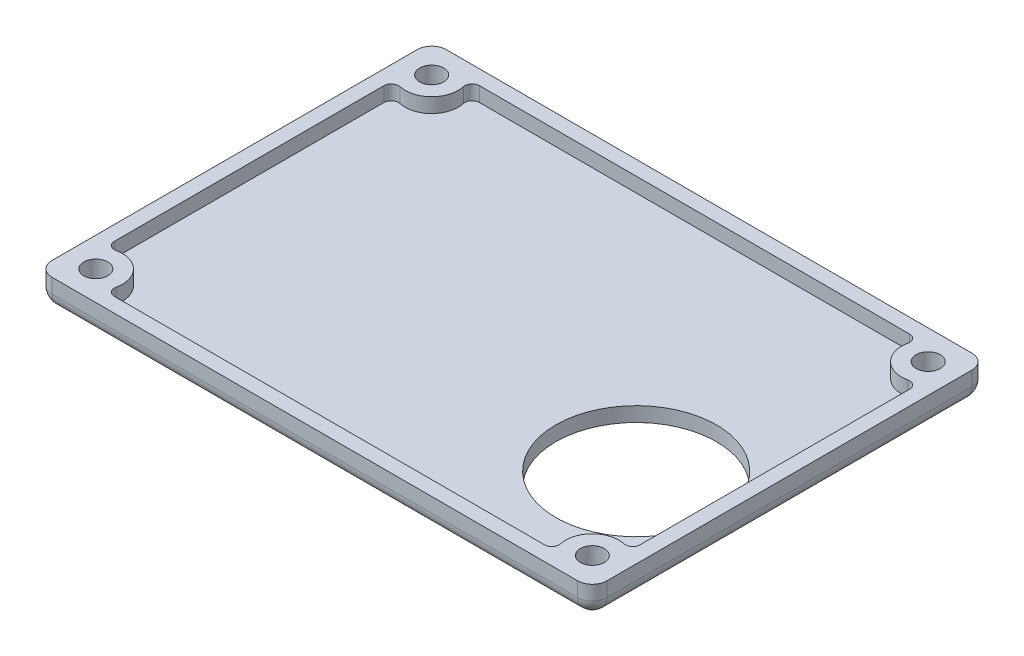
SolidWorks part; units mm, degrees
note: The reader was unsure of these and kept them because the rebuilt part matched: shared geometry of "Schizzo3<11>".
ref_plane "Piano frontale" through (0, 0, 0) normal (0, 0, 1) x (1, 0, 0)
ref_plane "Piano superiore" through (0, 0, 0) normal (0, 1, 0) x (1, 0, 0)
ref_plane "Piano destro" through (0, 0, 0) normal (1, 0, 0) x (0, 0, -1)
sketch "Schizzo1" plane through (0, 0, 0) normal (0, 1, 0) x (1, 0, 0)
  line L1 (-38, 27) -> (38, 27)
  line L2 (-38, 27) -> (-38, -27)
  line L3 (-38, -27) -> (38, -27)
  line L4 (38, 27) -> (38, -27)
  line L5 (-38, 27) -> (38, -27) construction
  line L6 (-38, -27) -> (38, 27) construction
  point P0 (0, 0)
  dimension "D1" = 76
  dimension "D2" = 54
extrude "Estrusione-Estrusione1" add sketch "Schizzo1" along normal blind 4
sketch "Schizzo2" plane through (0, 4, 0) normal (0, 1, 0) x (1, 0, 0)
  line L0 (38, 27) -> (-38, 27) construction
  line L1 (-36, 25) -> (36, 25)
  line L2 (-36, 25) -> (-36, -25)
  line L3 (-36, -25) -> (36, -25)
  line L4 (36, 25) -> (36, -25)
  line L5 (-36, 25) -> (36, -25) construction
  line L6 (-36, -25) -> (36, 25) construction
  line L7 (38, -27) -> (38, 27) construction
  point P0 (0, 0)
  dimension "D1" = 2
  dimension "D2" = 2
extrude "Taglio-Estrusione1" cut sketch "Schizzo2" against normal offset from surface (2 mm away) 2 up to face at (0, 0, 0)
sketch "Schizzo3" plane through (0, 2, 0) normal (0, 1, 0) x (1, 0, 0)
  line L2 (0, 42.9417) -> (0, -43.5578) construction
  line L3 (46.4844, 0) -> (-110.297, 0) construction
  line L10 (38, -27) -> (38, 27) construction
  line L13 (38, 27) -> (-38, 27) construction
  circle A8 centre (34, 23) radius 1.65
  circle A9 centre (34, 23) radius 3.65
  circle A10 centre (-34, 23) radius 3.65
  circle A13 centre (-34, 23) radius 1.65
  circle A18 centre (34, -23) radius 1.65
  circle A19 centre (34, -23) radius 3.65
  circle A20 centre (-34, -23) radius 1.65
  circle A21 centre (-34, -23) radius 3.65
  dimension "D2" = 3.3
  dimension "D4" = 2
  dimension "D1" = 4
  dimension "D3" = 4
extrude "Estrusione-Estrusione2" add sketch "Schizzo3" along normal up to surface (2 mm away) up to face at (0, 4, 0)
extrude "Taglio-Estrusione4" cut sketch "Schizzo3<11>" against normal through all contours A13 | A20 | A18 | A8
sketch "Schizzo3<11>" plane through (0, 2, 0) normal (0, 1, 0) x (1, 0, 0) same geometry as "Schizzo3"
sketch "Schizzo5" plane through (0, 0, 0) normal (0, -1, 0) x (1, 0, 0)
  line L0 (-38, 27) -> (38, 27) construction
  line L1 (38, 27) -> (38, -27) construction
  circle A0 centre (25, 8) radius 11
  dimension "D1" = 22
  dimension "D2" = 19
  dimension "D3" = 13
extrude "Taglio-Estrusione5" cut sketch "Schizzo5" against normal up to surface (2 mm away) up to face at (0, 2, 0)
fillet "Raccordo1" radius 2 8 edges at (-38, 2, -27) (38, 2, -27) (38, 2, 27) (-38, 2, 27) (-38, 0, 0) (0, 0, -27) (38, 0, 0) (0, 0, 27)
fillet "Raccordo2" radius 1 8 edges at (30.9467, 3, -25) (36, 3, -19.9467) (36, 3, 19.9467) (30.9467, 3, 25) (-30.9467, 3, 25) (-36, 3, 19.9467) (-36, 3, -19.9467) (-30.9467, 3, -25)
